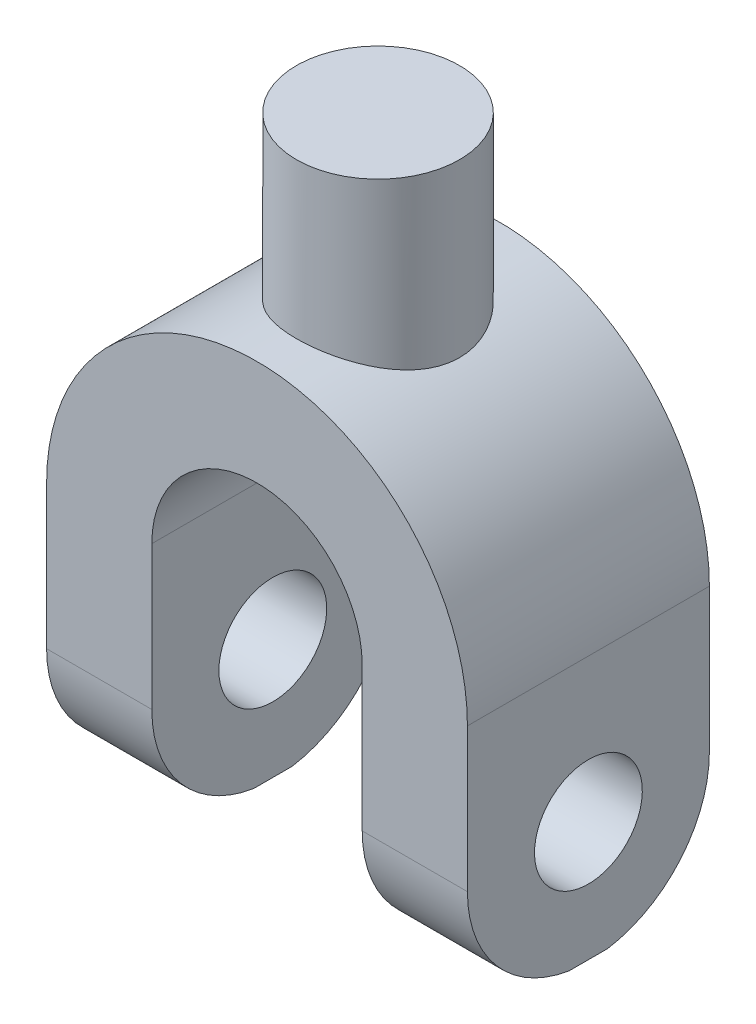
SolidWorks part; units mm, degrees
note: The reader was unsure of these and kept them because the rebuilt part matched: shared geometry of "Sketch1<4>".
ref_plane "Front Plane" through (0, 0, 0) normal (0, 0, 1) x (1, 0, 0)
ref_plane "Top Plane" through (0, 0, 0) normal (0, 1, 0) x (1, 0, 0)
ref_plane "Right Plane" through (0, 0, 0) normal (1, 0, 0) x (0, 0, -1)
sketch "Sketch1" plane through (0, 0, 0) normal (0, 0, 1) x (1, 0, 0)
  line L0 (-152.6091, 7.2646) -> (-152.6091, -56.2354)
  line L1 (-152.6091, -56.2354) -> (-127.2091, -56.2354)
  line L2 (-127.2091, -56.2354) -> (-127.2091, 7.2646)
  line L3 (-76.4091, -56.2354) -> (-51.0091, -56.2354)
  line L4 (-51.0091, -56.2354) -> (-51.0091, 7.2646)
  line L5 (-76.4091, -56.2354) -> (-76.4091, 7.2646)
  line L7 (-121.5021, 54.0922) -> (-121.5021, 95.4942)
  line L8 (-121.5021, 95.4942) -> (-101.8091, 95.4942)
  line L9 (-101.8091, 95.4942) -> (-101.8091, 58.0646) construction
  arc A0 (-127.2091, 7.2646) -> (-76.4091, 7.2646) centre (-101.8091, 7.2646) cw
  arc A1 (-152.6091, 7.2646) -> (-51.0091, 7.2646) centre (-101.8091, 7.2646) cw
  point P13 (-101.8091, 7.2646)
  dimension "D1" = 101.6
extrude "Boss-Extrude1" add sketch "Sketch1" along normal mid plane 58.42 contours A1 L0 L1 L2 A0 L5 L3 L4
revolve "Revolve1" add sketch "Sketch1<4>" angle 360 about L9
sketch "Sketch1<4>" plane through (0, 0, 0) normal (0, 0, 1) x (1, 0, 0) same geometry as "Sketch1"
sketch "Sketch3" plane through (-51.0091, 0, 0) normal (1, 0, 0) x (0, 0, -1)
  line L0 (-35.5738, -27.3983) -> (64.1947, -27.3983) construction
  line L1 (0, 7.2646) -> (0, -56.2354) construction
  line L2 (-29.21, -56.2354) -> (-29.21, 7.2646) construction
  line L3 (29.21, -56.2354) -> (29.21, 7.2646) construction
  circle A0 centre (0, -27.3983) radius 13.0169
  arc A1 (-29.21, -27.3983) -> (29.21, -27.3983) centre (0, -27.3983) ccw
  point P9 (29.21, -27.3983)
  line M2 (29.21, -56.2354) -> (29.21, 7.2646)
  line M4 (-29.21, 7.2646) -> (-29.21, -56.2354)
  line M5 (-29.21, -56.2354) -> (29.21, -56.2354)
extrude "Cut-Extrude1" cut sketch "Sketch3" against normal through all contours A0 L0 | L0 A0 | A1 M4 M5 | A1 M5 M2
